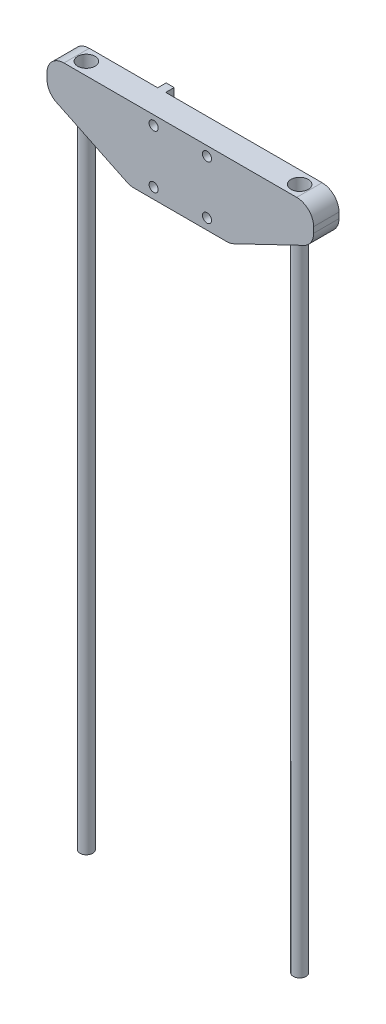
SolidWorks part; units mm, degrees
other "Markup2"
sketch "Sketch8"
other "Markup3"
sketch "Sketch15"
ref_plane "Front Plane" through (0, 0, 0) normal (0, 0, 1) x (1, 0, 0)
ref_plane "Top Plane" through (0, 0, 0) normal (0, 1, 0) x (1, 0, 0)
ref_plane "Right Plane" through (0, 0, 0) normal (1, 0, 0) x (0, 0, -1)
sketch "Sketch2" plane through (0, 0, 0) normal (0, 0, 1) x (1, 0, 0)
  line L0 (-40, 0) -> (-40, -243.6) construction
  line L1 (40, 0) -> (40, -243.6) construction
  line L2 (0, 48.6067) -> (0, -93.2297) construction
  line L3 (-50, 12.5) -> (-50, 0)
  line L4 (-50, 0) -> (-18.75, -15)
  line L5 (-18.75, -15) -> (18.75, -15)
  line L6 (18.75, -15) -> (50, 0)
  line L7 (-50, 12.5) -> (50, 12.5)
  line L8 (50, 12.5) -> (50, 0)
  line L10 (-42.3812, 0) -> (-37.6188, 0)
  line L11 (-42.3812, 0) -> (-42.3812, -243.6)
  line L12 (-42.3812, -243.6) -> (-37.6187, -243.6)
  line L13 (-37.6188, 0) -> (-37.6187, -243.6)
  line L14 (-10, 9) -> (10, 9) construction
  line L15 (-10, 9) -> (-10, -11) construction
  line L16 (-10, -11) -> (10, -11) construction
  line L17 (10, 9) -> (10, -11) construction
  line L18 (37.6188, -243.6) -> (42.3813, -243.6)
  line L19 (37.6188, -243.6) -> (37.6188, 0)
  line L20 (37.6188, 0) -> (42.3812, 0)
  line L21 (42.3813, -243.6) -> (42.3812, 0)
  dimension "D1" = 80
  dimension "D3" = 4.7625
  dimension "D4" = 20
  dimension "D5" = 20
  dimension "D6" = 228.6
  dimension "12.5" = 12.5
  dimension "D8" = 15
  dimension "D9" = 4
  dimension "D10" = 12.5
  dimension "D11" = 100
  dimension "D12" = 37.5
sketch "Sketch9" plane through (0, 0, 0) normal (0, 1, 0) x (1, 0, 0)
  line L0 (-40, 0) -> (-35, 0) construction
  line L2 (-40, 2.3812) -> (-35, 2.3812)
  line L3 (-40, -2.3812) -> (-35, -2.3812)
  line L4 (0, 20.7896) -> (0, -26.7229) construction
  line L5 (40, 0) -> (35, 0) construction
  line L6 (40, 2.3813) -> (35, 2.3813)
  line L7 (40, -2.3813) -> (35, -2.3813)
  line L8 (-37.5, 2.3812) -> (-37.5, -2.3812) construction
  line L9 (-42.3812, 0) -> (-37.6187, 0) construction
  line L10 (37.5, 2.3813) -> (37.5, -2.3813) construction
  arc A0 (-40, 2.3812) -> (-40, -2.3812) centre (-40, 0) ccw
  arc A1 (-35, -2.3812) -> (-35, 2.3812) centre (-35, 0) ccw
  arc A2 (40, 2.3813) -> (40, -2.3813) centre (40, 0) cw
  arc A3 (35, -2.3813) -> (35, 2.3813) centre (35, 0) cw
  circle A4 centre (-40, 0) radius 1.5
  circle A5 centre (40, 0) radius 1.5
  point P5 (-37.5, 0)
  point P15 (37.5, 0)
  dimension "D1" = 5
  dimension "D3" = 3
  dimension "D2" = 4.7625
sketch "Sketch3" plane through (0, 0, 0) normal (0, 0, 1) x (1, 0, 0)
  line L0 (-50, 12.5) -> (-50, 0) construction
  line L1 (-50, 0) -> (-18.75, -15) construction
  line L2 (-18.75, -15) -> (18.75, -15) construction
  line L3 (18.75, -15) -> (50, 0) construction
  line L4 (50, 12.5) -> (50, 0) construction
  line L5 (-50, 12.5) -> (50, 12.5) construction
  line L6 (-50, 12.5) -> (-50, 0)
  line L7 (-50, 0) -> (-18.75, -15)
  line L8 (-18.75, -15) -> (18.75, -15)
  line L9 (18.75, -15) -> (50, 0)
  line L10 (50, 12.5) -> (50, 0)
  line L11 (-50, 12.5) -> (50, 12.5)
extrude "Boss-Extrude1" add sketch "Sketch3" along normal mid plane 9.525
sketch "Sketch10" plane through (0, 0, 0) normal (0, 1, 0) x (1, 0, 0)
  line L0 (40, 2.3813) -> (35, 2.3813) construction
  line L1 (40, -2.3813) -> (35, -2.3813) construction
  line L2 (-40, 2.3812) -> (-35, 2.3812) construction
  line L3 (-40, -2.3812) -> (-35, -2.3812) construction
  line L4 (40, 2.3813) -> (35, 2.3813)
  line L5 (40, -2.3813) -> (35, -2.3813)
  line L6 (-40, 2.3812) -> (-35, 2.3812)
  line L7 (-40, -2.3812) -> (-35, -2.3812)
  arc A0 (35, 2.3813) -> (35, -2.3813) centre (35, 0) ccw construction
  arc A1 (40, -2.3813) -> (40, 2.3813) centre (40, 0) ccw construction
  arc A2 (-35, -2.3812) -> (-35, 2.3812) centre (-35, 0) ccw construction
  arc A3 (-40, 2.3812) -> (-40, -2.3812) centre (-40, 0) ccw construction
  arc A4 (35, 2.3813) -> (35, -2.3813) centre (35, 0) ccw
  arc A5 (40, -2.3813) -> (40, 2.3813) centre (40, 0) ccw
  arc A6 (-35, -2.3812) -> (-35, 2.3812) centre (-35, 0) ccw
  arc A7 (-40, 2.3812) -> (-40, -2.3812) centre (-40, 0) ccw
extrude "Cut-Extrude1" cut sketch "Sketch10" against normal blind 10
sketch "Sketch4" plane through (0, 0, 0) normal (0, 0, 1) x (1, 0, 0)
  line L0 (40, 0) -> (40, -243.6) construction
  line L1 (-40, 0) -> (-40, -243.6) construction
  line L2 (-42.3812, 0) -> (-42.3812, -243.6) construction
  line L3 (-42.3812, -243.6) -> (-37.6187, -243.6) construction
  line L4 (-37.6188, 0) -> (-37.6187, -243.6) construction
  line L5 (-42.3812, 0) -> (-37.6188, 0) construction
  line L6 (40, 0) -> (40, -243.6)
  line L7 (-40, 0) -> (-40, -243.6)
  line L8 (-42.3812, 0) -> (-42.3812, -243.6)
  line L9 (-42.3812, -243.6) -> (-40, -243.6)
  line L10 (-37.6188, 0) -> (-37.6187, -243.6) construction
  line L11 (-42.3812, 0) -> (-40, 0)
  line L12 (-40, -243.6) -> (-40, -275.6996) construction
  line L13 (-40, -243.6) -> (-37.6187, -243.6) construction
  line L14 (-40, 0) -> (-37.6188, 0) construction
  line L15 (40, -243.6) -> (40, -281.3243) construction
  line L16 (37.6188, -243.6) -> (42.3813, -243.6)
  line L17 (37.6188, -243.6) -> (37.6188, 0)
  line L18 (37.6188, 0) -> (42.3812, 0)
  line L19 (42.3813, -243.6) -> (42.3812, 0)
  line L20 (37.6188, -247.4505) -> (40, -247.4505) construction
revolve "Revolve1" add sketch "Sketch4" angle 360 about L12 region at (-41.1906, -121.8, 0)
revolve "Revolve2" add sketch "Sketch4<3>" angle 360 about L15 region at (38.8094, -121.8, 0)
sketch "Sketch4<3>" plane through (0, 0, 0) normal (0, 0, 1) x (1, 0, 0) same geometry as "Sketch4"
hole_wizard "M3 Clearance Hole1" positions "Sketch5" profile "Sketch6" hole size "M3" standard "ANSI Metric" end condition through all
sketch "Sketch5" plane through (0, 0, 4.7625) normal (0, 0, 1) x (1, 0, 0)
  point P0 (-10, 9)
  point P3 (-10, -11)
  point P6 (10, -11)
  point P9 (10, 9)
sketch "Sketch6" plane through (-10, 9, 4.7625) normal (1, 0, 0) x (0, -1, 0)
  line L0 (0, 0) -> (0, 9.525)
  line L1 (0, 9.525) -> (1.7, 9.525)
  line L2 (1.7, 9.525) -> (1.7, 0)
  line L5 (1.7, 0) -> (0, 0)
  line L11 (0, -6.35) -> (0, 107.95) construction
  dimension "Thru Hole Dia." = 3.4
  dimension "Thru Hole Depth" = 9.525
hole_wizard "CBORE for M3 SHCS2" positions "Sketch11" profile "Sketch12" counterbore size "M3" standard "ANSI Metric" end condition through all
sketch "Sketch11" plane through (0, 12.5, 0) normal (0, 1, 0) x (1, 0, 0)
  point P0 (-40, 0)
  point P3 (40, 0)
sketch "Sketch12" plane through (-40, 12.5, 0) normal (1, 0, 0) x (0, 0, 1)
  line L0 (0, 0) -> (0, 256.1)
  line L1 (0, 256.1) -> (1.8, 256.1)
  line L3 (1.8, 256.1) -> (1.8, 11)
  line L4 (1.8, 11) -> (3.25, 11)
  line L5 (3.25, 11) -> (3.25, 0)
  line L7 (3.25, 0) -> (0, 0)
  line L11 (0, -6.35) -> (0, 107.95) construction
  dimension "Thru Hole Dia." = 3.6
  dimension "Thru Hole Depth" = 256.1
  dimension "C'Bore Dia." = 6.5
  dimension "C'Bore Depth" = 11
hole_wizard "M3x0.5 Tapped Hole1" positions "Sketch13" profile "Sketch14" tap size "M3x0.5" standard "ANSI Metric"
sketch "Sketch13" plane through (0, 0, 0) normal (0, 1, 0) x (1, 0, 0)
  point P0 (-40, 0)
  point P3 (40, 0)
sketch "Sketch14" plane through (-40, 0, 0) normal (1, 0, 0) x (0, 0, 1)
  line L0 (0, 0) -> (0, 8.2511)
  line L1 (0, 8.2511) -> (1.25, 7.5)
  line L2 (1.25, 7.5) -> (1.25, 0)
  line L5 (1.25, 0) -> (0, 0)
  line L10 (0, 8.2511) -> (-1.25, 7.5) construction
  line L11 (0, -6.35) -> (0, 107.95) construction
  dimension "Tap Drill Dia." = 2.5
  dimension "Tap Drill Depth" = 7.5
  dimension "Drill Angle" = 118
fillet "Fillet1" radius 6.35 6 edges at (-18.75, -15, 0) (18.75, -15, 0) (50, 0, 0) (50, 12.5, 0) (-50, 12.5, 0) (-50, 0, 0)
sketch "Sketch16" plane through (0, 0, -4.7625) normal (0, 0, -1) x (-1, 0, 0)
  line L0 (-43.65, 12.5) -> (43.65, 12.5) construction
  line L1 (18, -12) -> (15, -12)
  line L2 (18, -12) -> (18, 12.5)
  line L3 (18, 12.5) -> (15, 12.5)
  line L4 (15, -12) -> (15, 12.5)
  line L6 (17.3049, -15) -> (-17.3049, -15) construction
  circle A0 centre (10, -11) radius 1.7 construction
  dimension "D1" = 5
  dimension "D2" = 3
  dimension "D3" = 3
extrude "Boss-Extrude2" add sketch "Sketch16" along normal blind 3.175
